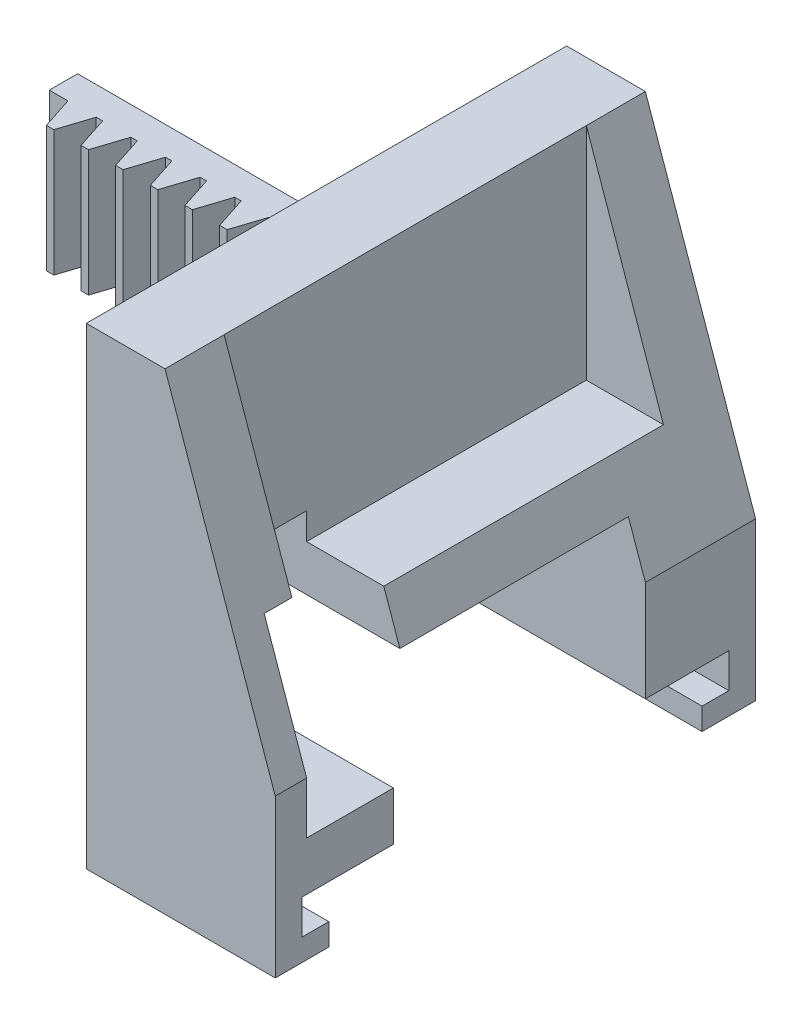
SolidWorks part; units mm, degrees
ref_plane "Front Plane" through (0, 0, 0) normal (0, 0, 1) x (1, 0, 0)
ref_plane "Top Plane" through (0, 0, 0) normal (0, 1, 0) x (1, 0, 0)
ref_plane "Right Plane" through (0, 0, 0) normal (1, 0, 0) x (0, 0, -1)
sketch "Sketch1" plane through (0, 0, 0) normal (0, 0, 1) x (1, 0, 0)
  line L0 (0, 0) -> (0, -30)
  line L1 (0, -30) -> (12, -30)
  line L2 (12, -30) -> (12, -20)
  line L3 (12, -20) -> (5, 0)
  line L4 (5, 0) -> (0, 0)
  dimension "D1" = 30
  dimension "D2" = 12
  dimension "D3" = 10
  dimension "D4" = 5
extrude "Boss-Extrude1" add sketch "Sketch1" against normal blind 30.5
sketch "Sketch4" plane through (0, 0, 0) normal (-1, 0, 0) x (0, 0, 1)
  line L0 (-30.5, 0) -> (-30.5, -30) construction
  line L1 (-23.5, -16.9179) -> (-7.5, -16.9179)
  line L2 (-23.5, -16.9179) -> (-23.5, -30.9179)
  line L3 (-23.5, -30.9179) -> (-7.5, -30.9179)
  line L4 (-7.5, -16.9179) -> (-7.5, -30.9179)
  point P4 (-23.5, -23.9179)
  dimension "D1" = 16
  dimension "D2" = 14
  dimension "D3" = 7
extrude "Cut-Extrude2" cut sketch "Sketch4" against normal blind 25 contours L2 L1 L4 L3
ref_plane "Plane1" through (0, 0, -15.25) normal (0, 0, 1) x (1, 0, 0)
sketch "Sketch6" plane through (0, 0, -15.25) normal (0, 0, 1) x (1, 0, 0)
  line L0 (5, 0) -> (5, -14)
  line L1 (5, -14) -> (9.9, -14)
  line L2 (12, -20) -> (5, 0) construction
  line L3 (9.9, -14) -> (5, 0)
  dimension "D1" = 14
extrude "Cut-Extrude4" cut sketch "Sketch6" against normal mid plane 23
ref_plane "Plane2" through (0, -22, 0) normal (0, 1, 0) x (1, 0, 0)
sketch "Sketch7" plane through (0, -22, 0) normal (0, 1, 0) x (1, 0, 0)
  line L0 (0, 27.45) -> (-28, 27.45)
  line L1 (0, 30.5) -> (0, 0) construction
  line L62 (-16.5, 15.25) -> (16.5, 15.25) construction
  line L162 (0, 27.45) -> (0, 25.65)
  line L172 (-28, 25.65) -> (-28, 27.45)
  line L238 (0, 25.65) -> (-28, 25.65)
  dimension "D2" = 28
  dimension "D3" = 1.8
  dimension "D7" = 12.2
sketch "Sketch8" plane through (0, 0, 0) normal (-1, 0, 0) x (0, 0, 1)
  line L0 (-8.9912, -12.3) -> (-1.9912, -12.3)
  line L2 (-7.5, -30) -> (0, -30) construction
  line L6 (-1.9912, -12.3) -> (-1.9912, -23.3)
  line L7 (-1.9912, -23.3) -> (-8.9912, -23.3)
  line L9 (-8.9912, -23.3) -> (-8.9912, -12.3)
  dimension "D1" = 7
  dimension "D2" = 11
  dimension "D3" = 6.7
extrude "Cut-Extrude5" cut sketch "Sketch8" against normal through all
sketch "Sketch9" plane through (0, 0, 0) normal (-1, 0, 0) x (0, 0, 1)
  line L0 (-7.5, -26.4) -> (-1.7, -26.4)
  line L1 (-7.5, -23.3) -> (-7.5, -30) construction
  line L2 (-1.7, -26.4) -> (-1.7, -28.6)
  line L3 (-1.7, -28.6) -> (-3.4, -28.6)
  line L4 (-3.4, -28.6) -> (-3.4, -30.2967)
  line L5 (-3.4, -30.2967) -> (-7.5, -30.2967)
  line L6 (-7.5, -30.2967) -> (-7.5, -26.4)
  line L7 (-7.5, -30) -> (0, -30) construction
  line L8 (-15.25, -6.6) -> (-15.25, 6.6) construction
  line L9 (-23, -30.2967) -> (-23, -26.4)
  line L10 (-27.1, -30.2967) -> (-23, -30.2967)
  line L11 (-27.1, -28.6) -> (-27.1, -30.2967)
  line L12 (-28.8, -28.6) -> (-27.1, -28.6)
  line L13 (-28.8, -26.4) -> (-28.8, -28.6)
  line L14 (-23, -26.4) -> (-28.8, -26.4)
  dimension "D1" = 5.8
  dimension "D2" = 2.2
  dimension "D3" = 1.4
  dimension "D4" = 1.7
extrude "Cut-Extrude6" cut sketch "Sketch9" against normal through all
extrude "Boss-Extrude3" add sketch "Sketch7" along normal blind 8
sketch "Sketch10" plane through (0, -14, 0) normal (0, 1, 0) x (1, 0, 0)
  line L0 (-0.8197, 25.65) -> (-1.4799, 23.6209)
  line L1 (-28, 25.65) -> (0, 25.65) construction
  line L2 (-1.4799, 23.6209) -> (-1.9539, 23.6209)
  line L3 (-1.9539, 23.6209) -> (-2.6141, 25.65)
  line L4 (-2.6141, 25.65) -> (-0.8197, 25.65)
  line L5 (-4.8141, 25.65) -> (-3.0197, 25.65)
  line L6 (-3.0197, 25.65) -> (-3.6799, 23.6209)
  line L7 (-3.6799, 23.6209) -> (-4.1539, 23.6209)
  line L8 (-4.1539, 23.6209) -> (-4.8141, 25.65)
  line L9 (-7.0141, 25.65) -> (-5.2197, 25.65)
  line L10 (-5.2197, 25.65) -> (-5.8799, 23.6209)
  line L11 (-5.8799, 23.6209) -> (-6.3539, 23.6209)
  line L12 (-6.3539, 23.6209) -> (-7.0141, 25.65)
  line L13 (-9.2141, 25.65) -> (-7.4197, 25.65)
  line L14 (-7.4197, 25.65) -> (-8.0799, 23.6209)
  line L15 (-8.0799, 23.6209) -> (-8.5539, 23.6209)
  line L16 (-8.5539, 23.6209) -> (-9.2141, 25.65)
  line L17 (-11.4141, 25.65) -> (-9.6197, 25.65)
  line L18 (-9.6197, 25.65) -> (-10.2799, 23.6209)
  line L19 (-10.2799, 23.6209) -> (-10.7539, 23.6209)
  line L20 (-10.7539, 23.6209) -> (-11.4141, 25.65)
  line L21 (-13.6141, 25.65) -> (-11.8197, 25.65)
  line L22 (-11.8197, 25.65) -> (-12.4799, 23.6209)
  line L23 (-12.4799, 23.6209) -> (-12.9539, 23.6209)
  line L24 (-12.9539, 23.6209) -> (-13.6141, 25.65)
  line L25 (-15.8141, 25.65) -> (-14.0197, 25.65)
  line L26 (-14.0197, 25.65) -> (-14.6799, 23.6209)
  line L27 (-14.6799, 23.6209) -> (-15.1539, 23.6209)
  line L28 (-15.1539, 23.6209) -> (-15.8141, 25.65)
  line L29 (-18.0141, 25.65) -> (-16.2197, 25.65)
  line L30 (-16.2197, 25.65) -> (-16.8799, 23.6209)
  line L31 (-16.8799, 23.6209) -> (-17.3539, 23.6209)
  line L32 (-17.3539, 23.6209) -> (-18.0141, 25.65)
  line L33 (-20.2141, 25.65) -> (-18.4197, 25.65)
  line L34 (-18.4197, 25.65) -> (-19.0799, 23.6209)
  line L35 (-19.0799, 23.6209) -> (-19.5539, 23.6209)
  line L36 (-19.5539, 23.6209) -> (-20.2141, 25.65)
  line L37 (-22.4141, 25.65) -> (-20.6197, 25.65)
  line L38 (-20.6197, 25.65) -> (-21.2799, 23.6209)
  line L39 (-21.2799, 23.6209) -> (-21.7539, 23.6209)
  line L40 (-21.7539, 23.6209) -> (-22.4141, 25.65)
  line L41 (-24.6141, 25.65) -> (-22.8197, 25.65)
  line L42 (-22.8197, 25.65) -> (-23.4799, 23.6209)
  line L43 (-23.4799, 23.6209) -> (-23.9539, 23.6209)
  line L44 (-23.9539, 23.6209) -> (-24.6141, 25.65)
  line L45 (-26.8141, 25.65) -> (-25.0197, 25.65)
  line L46 (-25.0197, 25.65) -> (-25.6799, 23.6209)
  line L47 (-25.6799, 23.6209) -> (-26.1539, 23.6209)
  line L48 (-26.1539, 23.6209) -> (-26.8141, 25.65)
extrude "Boss-Extrude4" add sketch "Sketch10" against normal blind 8
